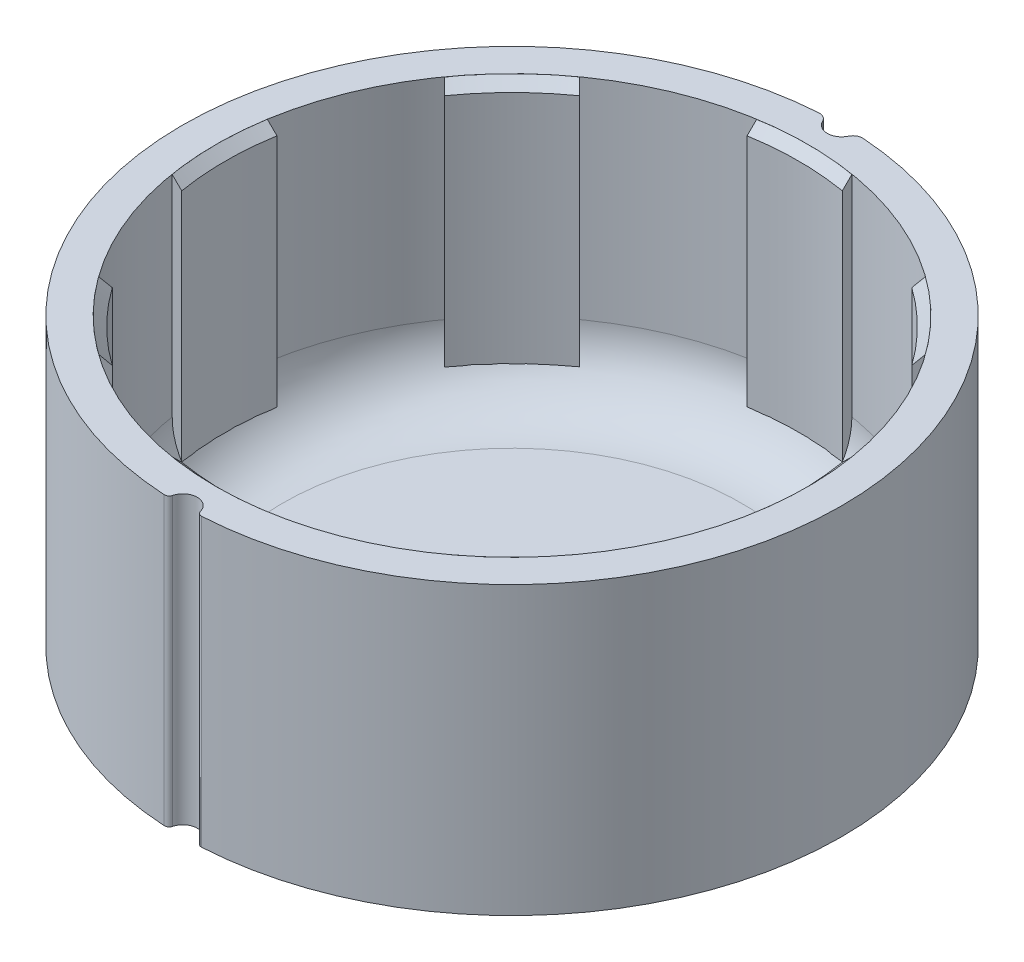
SolidWorks part; units mm, degrees
other "Markup1"
sketch "Sketch4"
other "Markup5"
sketch "Sketch8" plane through (34.5, 25, 34.4428) normal (0.0041, 0.9851, 0.1719) x (0.981, -0.0374, 0.1906)
other "Markup6"
sketch "Sketch9" plane through (34.5, 25, 34.4428) normal (0.0041, 0.9851, 0.1719) x (0.981, -0.0374, 0.1906)
other "Markup7"
sketch "Sketch10" plane through (-34.5, 25, 34.4428) normal (-0.125, 0.9874, 0.0969) x (0.5933, -0.0039, 0.805)
ref_plane "Front Plane" through (0, 0, 0) normal (0, 0, 1) x (1, 0, 0)
ref_plane "Top Plane" through (0, 0, 0) normal (0, 1, 0) x (1, 0, 0)
ref_plane "Right Plane" through (0, 0, 0) normal (1, 0, 0) x (0, 0, -1)
sketch "Sketch1" plane through (0, 0, 0) normal (0, 1, 0) x (1, 0, 0)
  line L3 (0, 0.002) -> (0, 3.7877) construction
  line L4 (0, 3.7877) -> (2.417, 3.7877)
  line L5 (0, 3.7877) -> (-2.417, 3.7877)
  arc A0 (1.9642, -34.442) -> (34.1982, 4.5552) centre (0, 0.002) ccw
  arc A2 (-2.417, 3.7877) -> (2.417, 3.7877) centre (0, 0.002) ccw
  circle A3 centre (0, 0.002) radius 34.5 construction
  arc A7 (-1.3541, 33.8562) -> (1.3541, 33.8562) centre (0, 34.5015) ccw
  arc A8 (34.1982, 4.5552) -> (2.3241, 34.4236) centre (0, 0.002) ccw
  arc A9 (-2.3241, 34.4236) -> (-34.1982, 4.5552) centre (0, 0.002) ccw
  arc A10 (-34.1982, 4.5552) -> (-1.9642, -34.442) centre (0, 0.002) ccw
  arc A11 (1.3541, 33.8562) -> (2.3241, 34.4236) centre (2.2568, 33.4259) cw
  arc A12 (-1.3541, 33.8562) -> (-2.3241, 34.4236) centre (-2.2568, 33.4259) ccw
  arc A13 (1.4518, -34.0686) -> (-1.4518, -34.0686) centre (0, -34.4457) ccw
  arc A14 (1.4518, -34.0686) -> (1.9642, -34.442) centre (1.9358, -33.9428) ccw
  arc A15 (-1.4518, -34.0686) -> (-1.9642, -34.442) centre (-1.9358, -33.9428) cw
  point P15 (1.4997, 34.4694)
  dimension "D2" = 4.834
  dimension "D3" = 4.4915
  dimension "D4" = 34.5
  dimension "D5" = 1
  dimension "D6" = 1.5
  dimension "D7" = 0.5
  dimension "D11" = 1.4997
sketch "Sketch2" plane through (0, 0, 0) normal (0, 1, 0) x (1, 0, 0)
  line L0 (0, 31) -> (0, 30) construction
  line L1 (-4.9837, 30.5968) -> (0, 31) construction
  line L2 (0, 31) -> (4.9837, 30.5968) construction
  line L3 (-4.9837, 30.5968) -> (-4.9837, 29.5831)
  line L6 (4.9837, 29.5831) -> (4.9837, 30.5968)
  circle A16 centre (0, 0) radius 31
  arc A18 (-4.9837, 29.5831) -> (4.9837, 29.5831) centre (0, 0) cw
  point P3 (0, 30)
  dimension "D1" = 62
  dimension "D2" = 5
  dimension "D3" = 1
extrude "Boss-Extrude1" add sketch "Sketch1" along normal blind 30 contours A10 A0 A8 A7 A9 A2 L5 L4 | L5 A2 L4 region at (0, 0, 0.1522) region at (2.2155, 0, 33.5591)
extrude "Cut-Extrude2" cut sketch "Sketch2" along normal up to next from offset 1 contours A16 | A16 region at (0, 0, 0.101)
extrude "Boss-Extrude2" add sketch "Sketch2<2>" along normal up to surface (30 mm away) separate body contours A16 region at (0, 0, -30.3632) up to face at (0, 30, 31)
sketch "Sketch2<2>" plane through (0, 0, 0) normal (0, 1, 0) x (1, 0, 0) same geometry as "Sketch2"
chamfer "Chamfer2" distance 1 angle 45 1 edges at (0, 30, -30)
pattern_circular "CirPattern2" count 8 over 360 about axis through (0, 30, 0) along (0, 1, 0) of bodies 106
fillet "Fillet2" radius 7 1 edges at (0, 1, 31)
